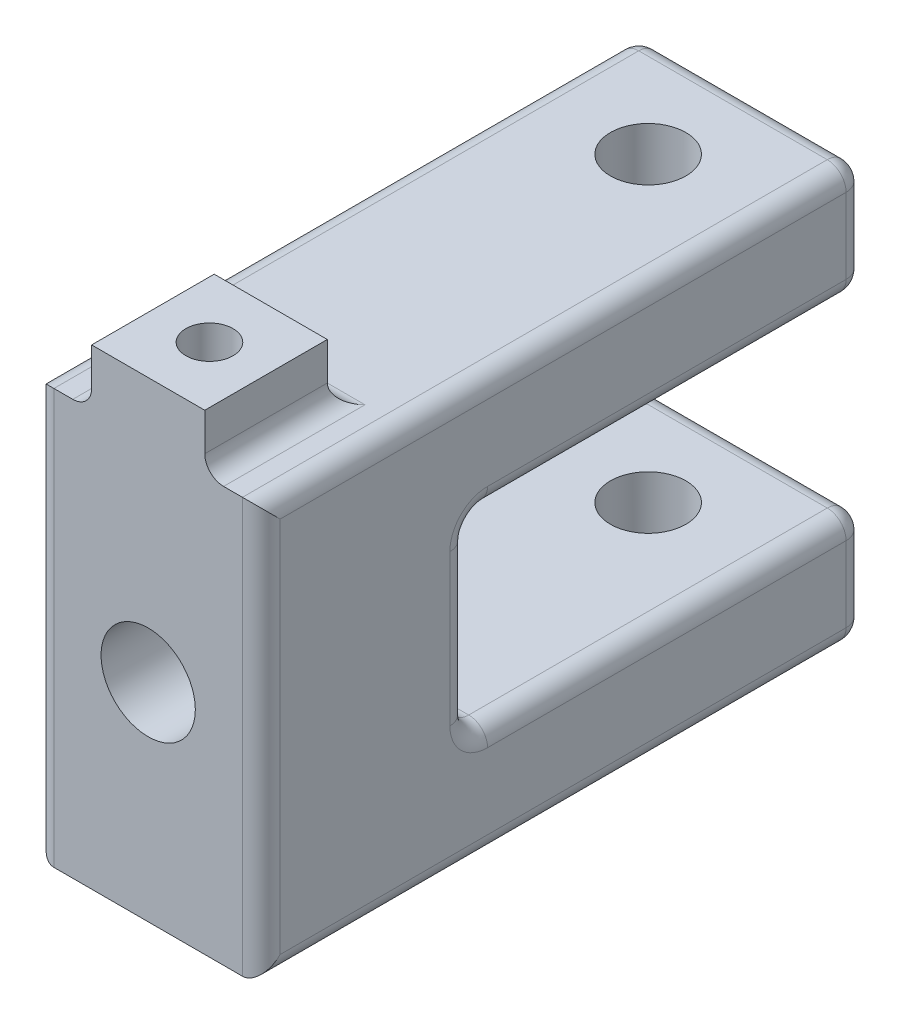
SolidWorks part; units mm, degrees
ref_plane "Front Plane" through (0, 0, 0) normal (0, 0, 1) x (1, 0, 0)
ref_plane "Top Plane" through (0, 0, 0) normal (0, 1, 0) x (1, 0, 0)
ref_plane "Right Plane" through (0, 0, 0) normal (1, 0, 0) x (0, 0, -1)
sketch "Sketch1" plane through (0, 0, 0) normal (1, 0, 0) x (0, 0, -1)
  line L0 (0, -22) -> (0, 22) construction
  line L1 (10.9228, 22) -> (-40.1115, 22)
  line L2 (10.9228, 22) -> (10.9228, 10)
  line L3 (10.9228, -22) -> (-53.1115, -22)
  line L4 (-40.1115, 22) -> (-53.1115, 22)
  line L5 (10.9228, -10) -> (10.9228, -22)
  line L6 (-5.471, -10) -> (-5.471, 10) construction
  line L7 (-31.1115, 10) -> (10.9228, 10)
  line L8 (-31.1115, 10) -> (-31.1115, -10)
  line L9 (-31.1115, -10) -> (10.9228, -10)
  line L10 (-51.5789, -22) -> (-51.5789, 28) construction
  line L11 (0, 0) -> (-53.1115, 0) construction
  line L12 (5.4027, 10) -> (5.4027, 22) construction
  line L13 (5.4027, -10) -> (5.4027, -22) construction
  line L16 (-40.1115, 22) -> (-40.1115, 28)
  line L17 (-40.1115, 28) -> (-53.1115, 28)
  line L18 (-53.1115, -22) -> (-53.1115, 28)
  point P10 (0, 0)
  point P12 (-5.471, 0)
  point P26 (-53.1115, 0)
  point P27 (-31.1115, 0)
  dimension "D1" = 50
  dimension "D2" = 12
  dimension "D3" = 20
  dimension "D4" = 22
  dimension "D5" = 13
extrude "Boss-Extrude2" add sketch "Sketch1" along normal blind 12 and the other way blind 12 contours L18 L3 L5 L9 L8 L7 L2 L1 L4 region at (0, 16, -10.1458)
extrude "Boss-Extrude3" add sketch "Sketch1<4>" along normal blind 6 and the other way blind 6 contours L18 L4 L16 L17 region at (0, 25, 46.6115)
sketch "Sketch1<4>" plane through (0, 0, 0) normal (1, 0, 0) x (0, 0, -1) same geometry as "Sketch1"
fillet "Fillet1" radius 2 25 edges at (12, -22, 21.0943) (12, 0, 53.1115) (12, 22, 21.0943) (0, -22, -10.9228) (0, -10, -10.9228) (12, -16, -10.9228) (12, -10, 10.0943) (12, 10, 10.0943) (12, 0, 31.1115) (6, 22, 46.6115) (0, 22, 40.1115) (-6, 22, 46.6115) (-12, 0, 53.1115) (-12, -22, 21.0943) (0, 10, 31.1115) (0, -10, 31.1115) (-12, -16, -10.9228) (-12, 0, 31.1115) (-12, -10, 10.0943) (-12, 10, 10.0943) (-12, 16, -10.9228) (-12, 22, 21.0943) (12, 16, -10.9228) (0, 10, -10.9228) (0, 22, -10.9228)
sketch "Sketch2" plane through (0, 28, 0) normal (0, 1, 0) x (1, 0, 0)
  line L0 (0, -53.1115) -> (0, -40.1115) construction
  line L1 (-6, -53.1115) -> (6, -53.1115) construction
  line L2 (6, -40.1115) -> (-6, -40.1115) construction
  circle A0 centre (0, -46.6115) radius 2.5
  point P9 (0, 0)
  point P10 (0, 0)
  point P11 (0, 0)
  point P12 (0, 0)
extrude "Cut-Extrude1" cut sketch "Sketch2" against normal blind 18
sketch "Sketch3" plane through (0, 0, 0) normal (1, 0, 0) x (0, 0, -1)
  line L0 (0, -19.932) -> (0, 22.8976) construction
sketch "Sketch4" plane through (0, 22, 0) normal (0, 1, 0) x (1, 0, 0)
  line L0 (0, -0.0772) -> (0, 10.9228) construction
  line L1 (-10, 10.9228) -> (10, 10.9228) construction
  circle A0 centre (0, -0.0772) radius 4
  point P3 (0, 0)
  dimension "D1" = 11
extrude "Cut-Extrude2" cut sketch "Sketch4" against normal through all both and the other way through all
sketch "Sketch5" plane through (0, 0, 53.1115) normal (0, 0, 1) x (1, 0, 0)
  circle A0 centre (0, 0) radius 5
  point P3 (0, 0)
  point P4 (0, 0)
  point P5 (1.1842, -4.002)
  point P6 (0, 0)
  point P7 (0, 0)
extrude "Cut-Extrude3" cut sketch "Sketch5" against normal blind 35
